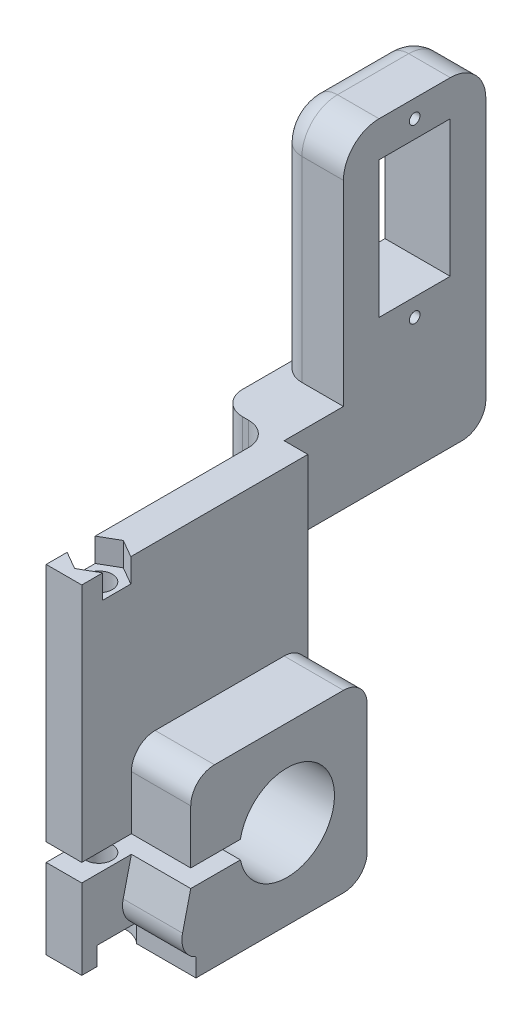
SolidWorks part; units mm, degrees
ref_plane "Front Plane" through (0, 0, 0) normal (0, 0, 1) x (1, 0, 0)
ref_plane "Top Plane" through (0, 0, 0) normal (0, 1, 0) x (1, 0, 0)
ref_plane "Right Plane" through (0, 0, 0) normal (1, 0, 0) x (0, 0, -1)
sketch "Sketch1" plane through (0, 0, 0) normal (1, 0, 0) x (0, 0, -1)
  line L0 (-58.4603, -42.4114) -> (-41.7184, -42.4114)
  line L2 (-10.3503, -1.9114) -> (-10.3503, 37.0886)
  line L3 (-10.3503, 37.0886) -> (13.6497, 37.0886)
  line L4 (-4.3503, 31.0886) -> (7.6497, 31.0886)
  line L5 (-18.0009, -48.9114) -> (13.6497, 37.0886) construction
  line L6 (-10.3503, 37.0886) -> (13.6497, -48.9114) construction
  line L7 (-20.3503, -58.9114) -> (-58.4603, -58.9114)
  line L8 (-58.4603, -45.4114) -> (-41.7184, -45.4114)
  line L10 (-58.4603, -58.9114) -> (-58.4603, -45.4114)
  line L11 (-4.3503, 31.0886) -> (-4.3503, 8.0886)
  line L12 (13.6497, 37.0886) -> (13.6497, -16.9114)
  line L13 (-4.3503, 8.0886) -> (7.6497, 8.0886)
  line L14 (7.6497, 31.0886) -> (7.6497, 8.0886)
  line L15 (-58.4603, -42.4114) -> (-58.4603, -28.9114)
  line L18 (13.6497, -16.9114) -> (-20.3503, -16.9114)
  line L19 (-10.3503, -1.9114) -> (-58.4603, -1.9114)
  line L20 (-58.4603, -28.9114) -> (-58.4603, -1.9114)
  line L21 (-20.3503, -58.9114) -> (-20.3503, -16.9114)
  arc A0 (-41.7184, -45.4114) -> (-41.7184, -42.4114) centre (-33.8603, -43.9114) ccw
  circle A1 centre (1.6497, 34.0886) radius 0.9
  circle A2 centre (1.6497, 5.0886) radius 0.9
  point P0 (0, 0)
  dimension "D3" = 16
  dimension "D11" = 1.8
  dimension "D12" = 1.8
  dimension "D1" = 30
  dimension "D2" = 15
  dimension "D4" = 38.11
  dimension "D5" = 24.6
  dimension "D6" = 24
  dimension "D7" = 12
  dimension "D8" = 6
  dimension "D9" = 6
  dimension "D10" = 23
  dimension "D13" = 3
  dimension "D14" = 3
  dimension "D15" = 6
  dimension "D16" = 6
  dimension "D17" = 13.5
  dimension "D18" = 3
  dimension "D19" = 86
  dimension "D20" = 25
  dimension "D21" = 42
extrude "Boss-Extrude1" add sketch "Sketch1" along normal blind 15
hole_wizard "CBORE for M4 Pan Head Machine Screw2" positions "Sketch6" profile "Sketch5" counterbore size "M4" standard "ANSI Metric" end condition through all
sketch "Sketch6" plane through (0, -58.9114, 0) normal (0, -1, 0) x (-1, 0, 0)
  line L0 (-15, -58.4603) -> (0, -58.4603) construction
  line L2 (-15, -58.4603) -> (-15, -20.3503) construction
  point P0 (-12, -52.5603)
  dimension "D1" = 5.9
  dimension "D2" = 3
sketch "Sketch5" plane through (12, -58.9114, 52.5603) normal (1, 0, 0) x (0, 0, -1)
  line L0 (0, 0) -> (0, 96)
  line L1 (0, 96) -> (2.25, 96)
  line L3 (2.25, 96) -> (2.25, 3.1)
  line L4 (2.25, 3.1) -> (4.5, 3.1)
  line L5 (4.5, 3.1) -> (4.5, 0)
  line L7 (4.5, 0) -> (0, 0)
  line L11 (0, -6.35) -> (0, 107.95) construction
  dimension "Thru Hole Dia." = 4.5
  dimension "Thru Hole Depth" = 96
  dimension "C'Bore Dia." = 9
  dimension "C'Bore Depth" = 3.1
sketch "Sketch7" plane through (0, -1.9114, 0) normal (0, 1, 0) x (1, 0, 0)
  line L1 (15.5534, -50.5166) -> (12.0068, -48.4611)
  line L2 (12.0068, -48.4611) -> (8.4534, -50.5048)
  line L3 (8.4534, -50.5048) -> (8.4466, -54.604)
  line L4 (8.4466, -54.604) -> (11.9932, -56.6595)
  line L5 (11.9932, -56.6595) -> (15.5466, -54.6158)
  line L6 (15.5466, -54.6158) -> (15.5534, -50.5166)
  circle A0 centre (12, -52.5603) radius 3.55 construction
  dimension "D1" = 7.1
extrude "Cut-Extrude2" cut sketch "Sketch7" against normal blind 4
sketch "Sketch11" plane through (0, 0, 0) normal (-1, 0, 0) x (0, 0, 1)
  line L1 (58.4603, -1.9114) -> (20.3503, -1.9114)
  line L2 (58.4603, -1.9114) -> (58.4603, -58.9114)
  line L3 (58.4603, -58.9114) -> (20.3503, -58.9114)
  line L4 (20.3503, -1.9114) -> (20.3503, -58.9114)
extrude "Cut-Extrude3" cut sketch "Sketch11" against normal blind 9
fillet "Fillet3" radius 6 2 edges at (7.5, 37.0886, 10.3503) (7.5, 37.0886, -13.6497)
fillet "Fillet4" radius 4 11 edges at (0, 14.5886, 10.3503) (0, 35.3312, 8.5929) (0, 37.0886, -1.6497) (0, 35.3312, -11.8923) (15, 14.5886, 10.3503) (15, 35.3312, 8.5929) (15, 37.0886, -1.6497) (15, 35.3312, -11.8923) (7.5, -16.9114, -13.6497) (0, 7.0886, -13.6497) (15, 7.0886, -13.6497)
sketch "Sketch13" plane through (15, 0, 0) normal (1, 0, 0) x (0, 0, -1)
  line L0 (-41.7184, -42.4114) -> (-50.0894, -42.4114)
  line L1 (-58.4603, -42.4114) -> (-41.7184, -42.4114) construction
  line L2 (-50.0894, -42.4114) -> (-50.0894, -29.3407)
  line L3 (-50.0894, -29.3407) -> (-20.3503, -29.3407)
  line L4 (-20.3503, -58.9114) -> (-20.3503, -16.9114) construction
  line L5 (-20.3503, -29.3407) -> (-20.3503, -58.9114)
  line L6 (-20.3503, -58.9114) -> (-49.2062, -58.9114)
  line L7 (-49.2062, -58.9114) -> (-49.2062, -55.8114) construction
  line L8 (-49.2062, -58.9114) -> (-20.3503, -58.9114) construction
  line L9 (-49.2062, -58.9114) -> (-49.2062, -55.8114)
  line L10 (-49.2062, -55.8114) -> (-52.5603, -55.8114)
  line L11 (-49.2062, -55.8114) -> (-55.9144, -55.8114) construction
  line L12 (-52.5603, -55.8114) -> (-50.0894, -45.4114)
  line L13 (-41.7184, -45.4114) -> (-58.4603, -45.4114) construction
  line L14 (-50.0894, -45.4114) -> (-41.7184, -45.4114)
  arc A0 (-41.7184, -45.4114) -> (-41.7184, -42.4114) centre (-33.8603, -43.9114) ccw
extrude "Boss-Extrude2" add sketch "Sketch13" along normal blind 10
fillet "Fillet2" radius 4 6 edges at (17, -58.9114, 20.3503) (9, -9.4114, 20.3503) (0, -9.4114, 20.3503) (20, -55.8114, 52.5603) (20, -29.3407, 20.3503) (20, -29.3407, 50.0894)
sketch "Sketch14" plane through (15, 0, 0) normal (1, 0, 0) x (0, 0, -1)
  line L0 (-20.3503, -33.3407) -> (-20.3503, -16.9114) construction
  line L1 (20.3503, 40.6593) -> (-20.3503, 40.6593)
  line L2 (20.3503, 40.6593) -> (20.3503, -29.3407)
  line L3 (20.3503, -29.3407) -> (-20.3503, -29.3407)
  line L4 (-20.3503, 40.6593) -> (-20.3503, -29.3407)
  point P0 (0, 0)
  dimension "D1" = 70
extrude "Cut-Extrude4" cut sketch "Sketch14" against normal blind 4
